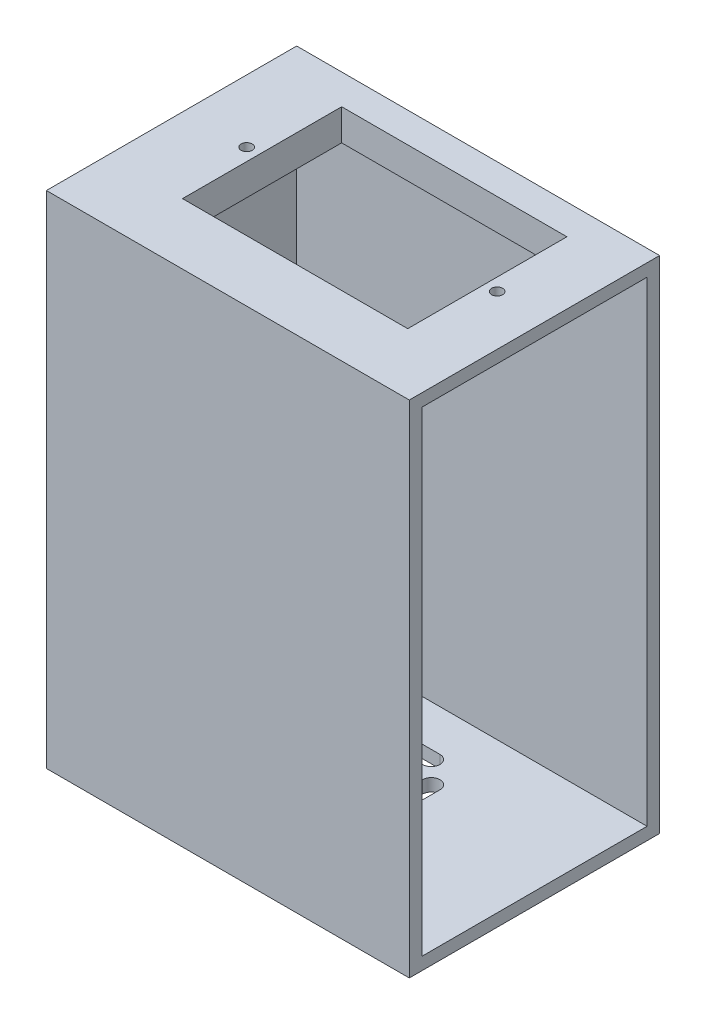
SolidWorks part; units mm, degrees
ref_plane "Front Plane" through (0, 0, 0) normal (0, 0, 1) x (1, 0, 0)
ref_plane "Top Plane" through (0, 0, 0) normal (0, 1, 0) x (1, 0, 0)
ref_plane "Right Plane" through (0, 0, 0) normal (1, 0, 0) x (0, 0, -1)
sketch "Sketch1" plane through (0, 0, 0) normal (0, 0, 1) x (1, 0, 0)
  line L1 (-38.1, -50.8) -> (38.1, -50.8)
  line L2 (-38.1, -50.8) -> (-38.1, 50.8)
  line L3 (-38.1, 50.8) -> (38.1, 50.8)
  line L4 (38.1, -50.8) -> (38.1, 50.8)
  line L5 (-38.1, -50.8) -> (38.1, 50.8) construction
  line L6 (-38.1, 50.8) -> (38.1, -50.8) construction
  point P0 (0, 0)
  dimension "D1" = 76.2
  dimension "D2" = 101.6
extrude "body" add sketch "Sketch1" along normal blind 50.8
sketch "Sketch2" plane through (0, 50.8, 0) normal (0, 1, 0) x (1, 0, 0)
  line L0 (38.1, 0) -> (-38.1, 0) construction
  line L1 (22.86, -38.4191) -> (-22.86, -38.4191)
  line L2 (22.86, -38.4191) -> (22.86, -6.1103)
  line L3 (22.86, -6.1103) -> (-22.86, -6.1103)
  line L4 (-22.86, -38.4191) -> (-22.86, -6.1103)
  line L5 (22.86, -38.4191) -> (-22.86, -6.1103) construction
  line L6 (22.86, -6.1103) -> (-22.86, -38.4191) construction
  point P0 (0, -22.2647)
  point P8 (0, 0)
  dimension "D1" = 32.3088
  dimension "D2" = 45.72
  dimension "D3" = 0
extrude "camera hole" cut sketch "Sketch2" against normal blind 6.35
shell "hollow" thickness 2.54 removed face at (0, 44.45, 22.2647)
sketch "centre of button holes" plane through (0, -50.8, 0) normal (0, -1, 0) x (-1, 0, 0)
  point P0 (0, -19.05)
  dimension "D1" = 19.05
sketch "Sketch4" plane through (0, -50.8, 0) normal (0, -1, 0) x (1, 0, 0)
  line L0 (6.35, 20.955) -> (6.35, 17.145) construction
  line L1 (8.128, 20.955) -> (8.128, 17.145)
  line L2 (4.572, 20.955) -> (4.572, 17.145)
  arc A0 (8.128, 20.955) -> (4.572, 20.955) centre (6.35, 20.955) ccw
  arc A1 (4.572, 17.145) -> (8.128, 17.145) centre (6.35, 17.145) ccw
  point P2 (6.35, 19.05)
  dimension "D3" = 1.778
  dimension "D1" = 6.35
  dimension "D2" = 3.81
extrude "single button leg hole" cut sketch "Sketch4" against normal up to next
ref_axis "axis of button" through (0, -50.8, 19.05) along (0, -1, 0)
pattern_circular "all button holes" count 4 over 360 about axis through (0, -50.8, 19.05) along (0, -1, 0) of "single button leg hole"
sketch "Sketch5" plane through (38.1, 0, 0) normal (1, 0, 0) x (0, 0, -1)
  line L1 (0, -50.8) -> (-50.8, -50.8)
  line L2 (0, -50.8) -> (0, 50.8)
  line L3 (0, 50.8) -> (-50.8, 50.8)
  line L4 (-50.8, -50.8) -> (-50.8, 50.8)
extrude "let folks see in" cut sketch "Sketch5" against normal blind 2.54
hole_wizard "#4-40 Tapped Hole1" positions "Sketch7" profile "Sketch6" tap size "#4-40" standard "ANSI Inch"
sketch "Sketch7" plane through (0, 50.8, 0) normal (0, 1, 0) x (1, 0, 0)
  point P0 (-25.4, -22.86)
  point P2 (25.4, -22.8169)
  dimension "D1" = 50.8
  dimension "D2" = 25.4
  dimension "D3" = 22.86
sketch "Sketch6" plane through (-25.4, 50.8, 22.86) normal (1, 0, 0) x (0, 0, 1)
  line L0 (0, 0) -> (0, 8.2992)
  line L1 (0, 8.2992) -> (1.1303, 7.62)
  line L2 (1.1303, 7.62) -> (1.1303, 0)
  line L5 (1.1303, 0) -> (0, 0)
  line L10 (0, 8.2992) -> (-1.1303, 7.62) construction
  line L11 (0, -6.35) -> (0, 107.95) construction
  dimension "Tap Drill Dia." = 2.2606
  dimension "Tap Drill Depth" = 7.62
  dimension "Drill Angle" = 118
cosmetic thread "Hole Thread1"
cosmetic thread "Hole Thread2"
